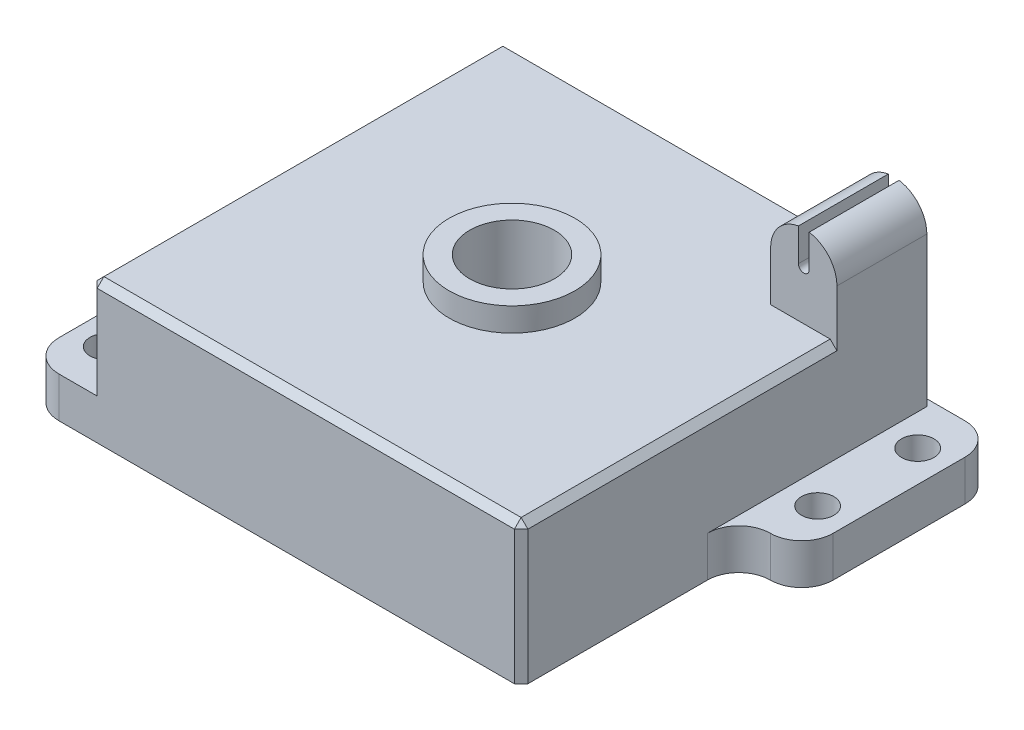
SolidWorks part; units mm, degrees
ref_plane "Plano frontal" through (0, 0, 0) normal (0, 0, 1) x (1, 0, 0)
ref_plane "Plano superior" through (0, 0, 0) normal (0, 1, 0) x (1, 0, 0)
ref_plane "Plano direito" through (0, 0, 0) normal (1, 0, 0) x (0, 0, -1)
sketch "Esboço1" plane through (0, 0, 0) normal (0, 1, 0) x (1, 0, 0)
  line L0 (-41.15, -1.7) -> (-31.85, -1.7)
  line L1 (-41.15, -30.5) -> (31.85, -30.5)
  line L2 (-41.15, -30.5) -> (-41.15, -1.7)
  line L3 (-31.85, 30.5) -> (41.15, 30.5)
  line L4 (41.15, 1.7) -> (41.15, 30.5)
  line L5 (-41.15, -30.5) -> (41.15, 30.5) construction
  line L6 (-41.15, 30.5) -> (41.15, -30.5) construction
  line L7 (-31.85, -1.7) -> (-31.85, 30.5)
  line L8 (31.85, -30.5) -> (31.85, 1.7)
  line L9 (31.85, 1.7) -> (41.15, 1.7)
  line L10 (-36.5, -1.7) -> (-36.5, -30.5) construction
  line L11 (36.5, 1.7) -> (36.5, 6.3) construction
  line L12 (36.5, 6.3) -> (36.5, 25.9) construction
  line L13 (36.5, 25.9) -> (36.5, 30.5) construction
  circle A0 centre (-36.5, -8.7) radius 2.4
  circle A1 centre (-36.5, -23.5) radius 2.4
  circle A2 centre (36.5, 8.7) radius 2.4
  circle A3 centre (36.5, 23.5) radius 2.4
  point P0 (0, 0)
  point P18 (-36.5, -6.3)
  point P20 (-36.5, -25.9)
  dimension "D6" = 4.8
  dimension "D1" = 82.3
  dimension "D2" = 61
  dimension "D3" = 32.2
  dimension "D4" = 9.3
  dimension "D5" = 36.546
  dimension "D7" = 4.6
  dimension "D8" = 4.6
  dimension "D9" = 4.6
extrude "Ressalto-extrusão1" add sketch "Esboço1" along normal blind 6
sketch "Esboço2" plane through (0, 6, 0) normal (0, 1, 0) x (1, 0, 0)
  line L1 (-31.85, 30.5) -> (31.85, 30.5)
  line L2 (-31.85, 30.5) -> (-31.85, -30.5)
  line L3 (-31.85, -30.5) -> (31.85, -30.5)
  line L4 (31.85, 30.5) -> (31.85, -30.5)
extrude "Ressalto-extrusão2" add sketch "Esboço2" along normal offset from surface (14.8 mm away) 20.8 up to face at (36.5, 0, -6.3)
chamfer "Chanfro1" distance 1 angle 45 8 edges at (-31.85, 20.8, 0) (-31.85, 13.4, 30.5) (0, 20.8, 30.5) (31.85, 10.4, 30.5) (31.85, 20.8, 0) (31.85, 13.4, -30.5) (0, 20.8, -30.5) (-31.85, 10.4, -30.5)
sketch "Esboço3" plane through (0, 20.8, 0) normal (0, 1, 0) x (1, 0, 0)
  circle A0 centre (0, 0) radius 6.25
  dimension "D1" = 12.5
extrude "Corte-extrusão1" cut sketch "Esboço3" against normal blind 16.8 contours A0
fillet "Filete1" radius 4.65 6 edges at (41.15, 3, -30.5) (41.15, 3, -1.7) (31.85, 3, -1.7) (-31.85, 3, 1.7) (-41.15, 3, 1.7) (-41.15, 3, 30.5)
ref_plane "Plano1" through (0, 0, -29.5) normal (0, 0, -1) x (-1, 0, 0)
sketch "Esboço4" plane through (0, 0, -29.5) normal (0, 0, -1) x (-1, 0, 0)
  line L1 (-31.85, 19.8) -> (-22.05, 19.8)
  line L2 (-31.85, 19.8) -> (-31.85, 28.1)
  line L4 (-22.05, 19.8) -> (-22.05, 28.1)
  line L5 (-36.5, 0) -> (30.85, 0) construction
  line L9 (-26.95, 30.7833) -> (-26.95, 28.1) construction
  line L11 (-27.75, 32.9343) -> (-27.75, 30.7833)
  line L13 (-26.15, 32.9343) -> (-26.15, 30.7833)
  line L14 (-27.75, 30.7833) -> (-26.15, 30.7833) construction
  arc A0 (-22.05, 28.1) -> (-26.15, 32.9343) centre (-26.95, 28.1) ccw
  arc A2 (-27.75, 30.7833) -> (-26.15, 30.7833) centre (-26.95, 28.1) ccw
  arc A3 (-27.75, 32.9343) -> (-31.85, 28.1) centre (-26.95, 28.1) ccw
  point P5 (0, 0)
  dimension "D2" = 28.1
  dimension "D3" = 5.6
  dimension "D1" = 9.8
  dimension "D4" = 1.6
extrude "Ressalto-extrusão4" add sketch "Esboço4" against normal blind 13.3
sketch "Esboço5" plane through (0, 0, -16.2) normal (0, 0, 1) x (1, 0, 0)
  line L2 (26.15, 30.7833) -> (26.15, 28.1)
  line L4 (27.75, 30.7833) -> (27.75, 28.1)
  arc A0 (26.15, 28.1) -> (27.75, 28.1) centre (26.95, 28.1) ccw
  arc A2 (26.15, 30.7833) -> (27.75, 30.7833) centre (26.95, 28.1) ccw construction
  arc A3 (26.15, 30.7833) -> (27.75, 30.7833) centre (26.95, 28.1) ccw
extrude "Ressalto-extrusão5" add sketch "Esboço5" against normal blind 2.2
sketch "Esboço6" plane through (0, 4, 0) normal (0, 1, 0) x (1, 0, 0)
  line L0 (0, 0) -> (6.25, 0) construction
  line L1 (0, 0) -> (3.125, -5.4127) construction
  line L2 (0, 0) -> (-3.125, -5.4127) construction
  line L3 (0, 0) -> (-5.25, 0) construction
  line L4 (0, 0) -> (-3.125, 5.4127) construction
  line L5 (0, 0) -> (3.125, 5.4127) construction
  line L6 (-5.25, 0) -> (-6.25, 0) construction
  line L7 (2.625, -4.5466) -> (3.125, -5.4127) construction
  line L8 (-2.625, -4.5466) -> (-3.125, -5.4127) construction
  line L9 (-3.0113, -4.3005) -> (-3.5849, -5.1197)
  line L10 (3.0113, -4.3005) -> (3.5849, -5.1197)
  line L11 (0, 0) -> (-3.0113, -4.3005) construction
  line L12 (0, 0) -> (3.0113, -4.3005) construction
  circle A1 centre (0, 0) radius 6.25 construction
  circle A2 centre (0, 0) radius 6.25 construction
  arc A3 (3.0113, -4.3005) -> (-3.0113, -4.3005) centre (0, 0) ccw
  arc A4 (3.5849, -5.1197) -> (-3.5849, -5.1197) centre (0, 0) ccw
  arc A5 (-2.625, -4.5466) -> (2.625, -4.5466) centre (0, 0) ccw construction
  arc A6 (-3.125, -5.4127) -> (3.125, -5.4127) centre (0, 0) ccw construction
  arc A7 (2.625, -4.5466) -> (3.0113, -4.3005) centre (0, 0) ccw construction
  arc A8 (3.125, -5.4127) -> (3.5849, -5.1197) centre (0, 0) ccw construction
  arc A9 (-3.0113, -4.3005) -> (-2.625, -4.5466) centre (0, 0) ccw construction
  arc A10 (-3.5849, -5.1197) -> (-3.125, -5.4127) centre (0, 0) ccw construction
  point P16 (0, 0)
  dimension "D2" = 1
  dimension "D3" = 5
  dimension "D4" = 5
  dimension "D1" = 6
extrude "Ressalto-extrusão6" add sketch "Esboço6" along normal blind 2.2
sketch "Esboço7" plane through (0, 20.8, 0) normal (0, 1, 0) x (1, 0, 0)
  circle A0 centre (0, 0) radius 9.3
  circle A1 centre (0, 0) radius 6.25 construction
  circle A2 centre (0, 0) radius 6.25
  dimension "D1" = 18.6
extrude "Ressalto-extrusão7" add sketch "Esboço7" along normal blind 3.5
